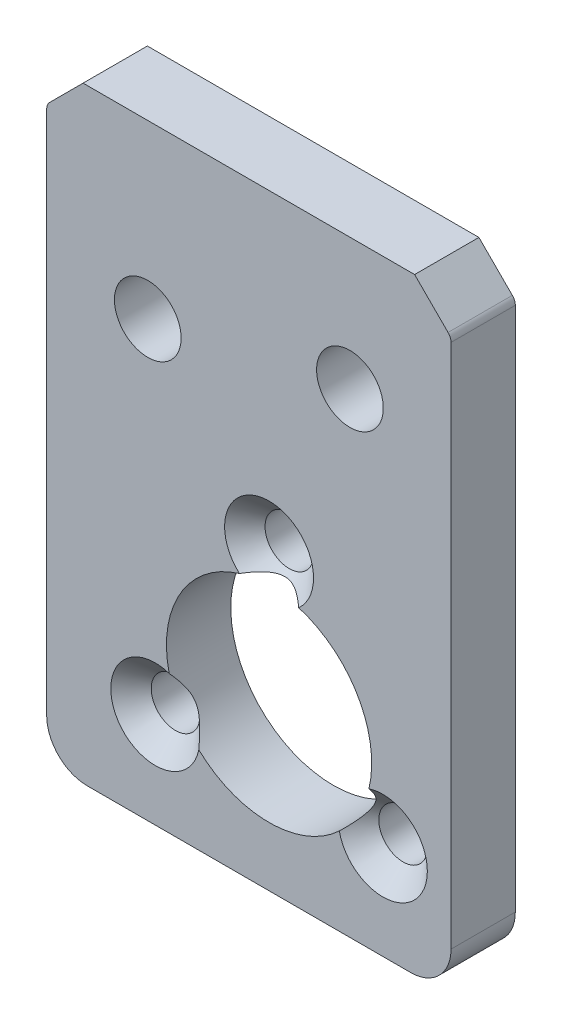
SolidWorks part; units mm, degrees
ref_plane "Front Plane" through (0, 0, 0) normal (0, 0, 1) x (1, 0, 0)
ref_plane "Top Plane" through (0, 0, 0) normal (0, 1, 0) x (1, 0, 0)
ref_plane "Right Plane" through (0, 0, 0) normal (1, 0, 0) x (0, 0, -1)
sketch "Sketch12" plane through (0, 0, 0) normal (0, 0, 1) x (1, 0, 0)
  line L0 (-20, -30) -> (0, -30)
  line L1 (-20, -30) -> (-20, 0)
  line L2 (0, -30) -> (0, 0)
  line L3 (-20, 0) -> (0, 0)
  line L4 (-9, -15.5) -> (-14.6292, -25.25) construction
  line L5 (-14.6292, -25.25) -> (-3.3708, -25.25) construction
  line L6 (-3.3708, -25.25) -> (-9, -15.5) construction
  circle A0 centre (-9, -22) radius 6.5 construction
  circle A6 centre (-9, -22) radius 5.075
  circle A7 centre (-5, -6.5) radius 1.65
  circle A8 centre (-15, -8.5) radius 1.65
  point P8 (-3.3708, -25.25)
  point P11 (-14.6292, -25.25)
  point P13 (-9, -15.5)
  dimension "D1" = 3.3
  dimension "D8" = 10.15
  dimension "D9" = 13
  dimension "D2" = 30
  dimension "D3" = 6.5
  dimension "D4" = 8.5
  dimension "D5" = 5
  dimension "D6" = 15
  dimension "D7" = 22
  dimension "D10" = 9
  dimension "D11" = 20
extrude "Boss-Extrude3" add sketch "Sketch12" along normal blind 3.18
hole_wizard "CSK for M2 Flat Head Machine Screw2" positions "Sketch13" profile "Sketch15" countersink size "M2" standard "ANSI Metric" end condition through all
sketch "Sketch13" plane through (0, 0, 3.18) normal (0, 0, 1) x (1, 0, 0)
  point P0 (-9, -15.5)
  point P3 (-14.6292, -25.25)
  point P6 (-3.3708, -25.25)
sketch "Sketch15" plane through (-9, -15.5, 3.18) normal (1, 0, 0) x (0, -1, 0)
  line L0 (0, 0) -> (0, 3.18)
  line L1 (0, 3.18) -> (1.2, 3.18)
  line L2 (1.2, 3.18) -> (1.2, 1)
  line L3 (1.2, 1) -> (2.2, 0)
  line L5 (2.2, 0) -> (0, 0)
  line L6 (-1.2, 1) -> (-2.2, 0) construction
  line L11 (0, -6.35) -> (0, 107.95) construction
  dimension "Thru Hole Dia." = 2.4
  dimension "Thru Hole Depth" = 3.18
  dimension "Near C'Sink Dia." = 4.4
  dimension "Near C'Sink Angle" = 90
chamfer "Chamfer1" distance 1.8 angle 45 2 edges at (-20, 0, 1.59) (0, 0, 1.59)
fillet "Fillet3" radius 0.5 2 edges at (-20, -1.8, 1.59) (0, -1.8, 1.59)
fillet "Fillet4" radius 2 2 edges at (-20, -30, 1.59) (0, -30, 1.59)
